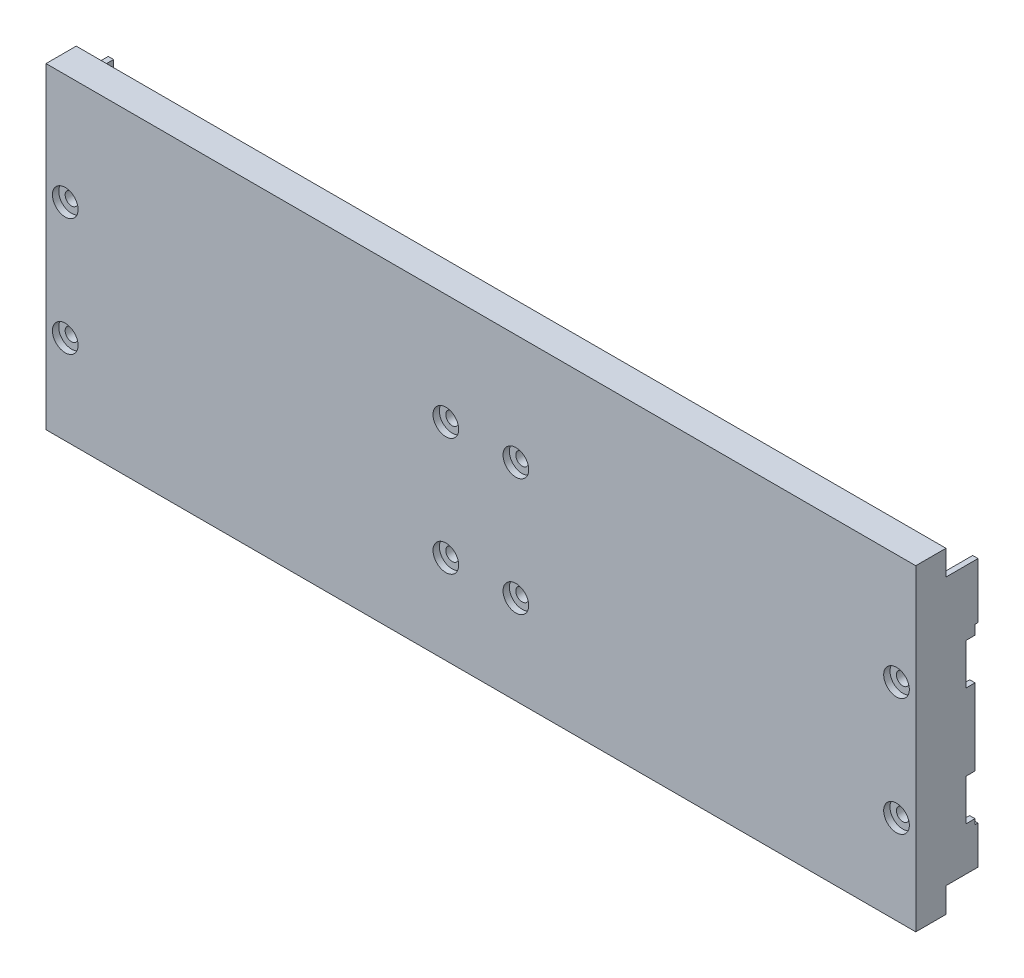
SolidWorks part; units mm, degrees
ref_plane "Front Plane" through (0, 0, 0) normal (0, 0, 1) x (1, 0, 0)
ref_plane "Top Plane" through (0, 0, 0) normal (0, 1, 0) x (1, 0, 0)
ref_plane "Right Plane" through (0, 0, 0) normal (1, 0, 0) x (0, 0, -1)
sketch "Sketch1" plane through (0, 0, 0) normal (0, 0, 1) x (1, 0, 0)
  line L0 (-30.5002, 35.0258) -> (66.0198, 35.0258) construction
  line L1 (67.5438, 35.0258) -> (-139.0852, 35.0258)
  line L2 (67.5438, 35.0258) -> (67.5438, -28.4742)
  line L3 (67.5438, -28.4742) -> (-139.0852, -28.4742)
  line L4 (-139.0852, 35.0258) -> (-139.0852, -28.4742)
  line L5 (66.0198, -28.4742) -> (-30.5002, -28.4742) construction
  line L6 (-137.5612, -28.4742) -> (-137.5612, 35.0258) construction
  line L7 (66.0198, 35.0258) -> (66.0198, -28.4742) construction
  dimension "D1" = 1.524
  dimension "D2" = 1.524
extrude "base" add sketch "Sketch1" along normal blind 5.08
sketch "Sketch2" plane through (0, 0, 0) normal (0, 0, -1) x (-1, 0, 0)
  line L0 (-67.5438, 35.0258) -> (139.0852, 35.0258) construction
  line L1 (137.5612, -26.9502) -> (-66.0198, -26.9502)
  line L2 (137.5612, -26.9502) -> (137.5612, 33.5018)
  line L3 (137.5612, 33.5018) -> (-66.0198, 33.5018)
  line L4 (-66.0198, -26.9502) -> (-66.0198, 33.5018)
  line L5 (-67.5438, -28.4742) -> (-67.5438, 35.0258) construction
  line L6 (139.0852, -28.4742) -> (-67.5438, -28.4742) construction
  line L7 (139.0852, 35.0258) -> (139.0852, -28.4742) construction
  dimension "D1" = 1.524
  dimension "D2" = 1.524
  dimension "D3" = 1.524
  dimension "D4" = 1.524
extrude "hollow" cut sketch "Sketch2" against normal blind 2
sketch "Sketch3" plane through (0, 0, 0) normal (0, 0, -1) x (-1, 0, 0)
  line L0 (-67.5438, 35.0258) -> (139.0852, 35.0258) construction
  line L1 (137.8152, 35.0258) -> (139.0852, 35.0258)
  line L2 (137.8152, 35.0258) -> (137.8152, -28.4742)
  line L3 (137.8152, -28.4742) -> (139.0852, -28.4742)
  line L4 (139.0852, 35.0258) -> (139.0852, -28.4742)
  line L5 (139.0852, -28.4742) -> (-67.5438, -28.4742) construction
  line L7 (139.0852, 35.0258) -> (139.0852, -28.4742) construction
  line L9 (-67.5438, 35.0258) -> (-66.2738, 35.0258)
  line L10 (-67.5438, 35.0258) -> (-67.5438, -28.4742)
  line L11 (-67.5438, -28.4742) -> (-66.2738, -28.4742)
  line L12 (-66.2738, 35.0258) -> (-66.2738, -28.4742)
  dimension "D1" = 1.27
  dimension "D2" = 1.27
extrude "end pieces" add sketch "Sketch3" along normal blind 9
sketch "Sketch7" plane through (67.5438, 0, 0) normal (1, 0, 0) x (0, 0, -1)
  line L0 (9, 35.0258) -> (9, -28.4742) construction
  line L1 (6.7986, 9.8068) -> (9, 9.8068)
  line L2 (6.7986, 9.8068) -> (6.7986, 19.6048)
  line L3 (6.7986, 19.6048) -> (9, 19.6048)
  line L4 (9, 9.8068) -> (9, 19.6048)
  line L5 (6.9986, 19.4048) -> (16.7986, 19.4048) construction
  line L6 (6.9986, 19.4048) -> (6.9986, 10.0068) construction
  line L7 (6.9986, 10.0068) -> (16.7986, 10.0068) construction
  line L8 (6.9986, -17.9332) -> (16.7986, -17.9332) construction
  line L9 (6.7986, -18.1332) -> (9, -18.1332)
  line L10 (6.7986, -18.1332) -> (6.7986, -8.3352)
  line L11 (6.7986, -8.3352) -> (9, -8.3352)
  line L12 (9, -18.1332) -> (9, -8.3352)
  dimension "D1" = 0.2
  dimension "D2" = 0.2
  dimension "D3" = 0.2
  dimension "D4" = 0.2
extrude "where top intrudes" cut sketch "Sketch7" against normal through all
sketch "cable stop wings" [suppressed] plane through (0, 0, 5.08) normal (0, 0, 1) x (1, 0, 0)
  line L0 (-139.0852, 35.0258) -> (-139.0852, -28.4742) construction
  line L1 (-139.0852, -28.4742) -> (67.5438, -28.4742)
  line L2 (-139.0852, -28.4742) -> (-139.0852, -46.2542)
  line L3 (-139.0852, -46.2542) -> (67.5438, -46.2542)
  line L4 (67.5438, -28.4742) -> (67.5438, -46.2542)
  line L5 (67.5438, -28.4742) -> (67.5438, 35.0258) construction
  line L6 (-139.0852, -28.4742) -> (67.5438, -28.4742) construction
  line L8 (-139.0852, 35.0258) -> (67.5438, 35.0258)
  line L9 (-139.0852, 35.0258) -> (-139.0852, 52.8058)
  line L10 (-139.0852, 52.8058) -> (67.5438, 52.8058)
  line L11 (67.5438, 35.0258) -> (67.5438, 52.8058)
  dimension "D1" = 17.78
extrude "cable stop wing boss" [suppressed] add sketch "cable stop wings" against normal blind 1.5 separate body
sketch "cable stop wings alt" plane through (0, 0, 5.08) normal (0, 0, 1) x (1, 0, 0)
  line L1 (-139.0852, -28.4742) -> (67.5438, -28.4742)
  line L2 (-139.0852, -28.4742) -> (-139.0852, -33.4742)
  line L3 (-139.0852, -33.4742) -> (67.5438, -33.4742)
  line L4 (67.5438, -28.4742) -> (67.5438, -33.4742)
  line L5 (67.5438, 35.0258) -> (-139.0852, 35.0258) construction
  line L6 (-139.0852, -28.4742) -> (67.5438, -28.4742) construction
  line L8 (-139.0852, 35.0258) -> (67.5438, 35.0258)
  line L9 (-139.0852, 35.0258) -> (-139.0852, 40.0258)
  line L10 (-139.0852, 40.0258) -> (67.5438, 40.0258)
  line L11 (67.5438, 35.0258) -> (67.5438, 40.0258)
  line L12 (67.5438, -28.4742) -> (67.5438, 35.0258) construction
  line L13 (-139.0852, 35.0258) -> (-139.0852, -28.4742) construction
  dimension "D1" = 5
extrude "cable stop wing boss alt" add sketch "cable stop wings alt" against normal blind 1.5
sketch "Sketch4" plane through (0, 0, 2) normal (0, 0, -1) x (-1, 0, 0)
  circle A0 centre (-62.9718, 14.7058) radius 2.794
  circle A1 centre (-62.9718, -13.2342) radius 2.794
  circle A2 centre (27.4522, -13.2342) radius 2.794
  circle A3 centre (44.0892, -13.2342) radius 2.794
  circle A4 centre (27.4522, 14.7058) radius 2.794
  circle A5 centre (44.0892, 14.7058) radius 2.794
  circle A6 centre (134.5132, 14.7058) radius 2.794
  circle A7 centre (134.5132, -13.2342) radius 2.794
  dimension "D1" = 5.588
extrude "screw bosses" add sketch "Sketch4" along normal up to surface (2 mm away) up to face at (-35.7707, 3.2758, 0)
sketch "Sketch5" plane through (0, 0, 0) normal (0, 0, -1) x (-1, 0, 0)
  circle A0 centre (-62.9718, 14.7058) radius 1.524
  circle A1 centre (-62.9718, -13.2342) radius 1.524
  circle A2 centre (27.4522, 14.7058) radius 1.524
  circle A3 centre (27.4522, -13.2342) radius 1.524
  circle A4 centre (44.0892, -13.2342) radius 1.524
  circle A5 centre (134.5132, 14.7058) radius 1.524
  circle A6 centre (134.5132, -13.2342) radius 1.524
  circle A7 centre (44.0892, 14.7058) radius 1.524
  dimension "D1" = 3.048
extrude "screw holes" cut sketch "Sketch5" against normal through all
sketch "wing extensions" [suppressed] plane through (0, 0, 5.08) normal (0, 0, -1) x (-1, 0, 0)
  line L0 (136.3082, -28.3942) -> (136.3082, -19.3942) construction
  line L1 (-73.6398, 52.8058) -> (-66.2908, 52.8058)
  line L2 (-73.6398, 52.8058) -> (-73.6398, 35.0258)
  line L3 (-73.6398, 35.0258) -> (-66.2908, 35.0258)
  line L4 (145.1812, 52.8058) -> (145.1812, 35.0258)
  line L6 (137.5612, -26.9502) -> (137.5612, 33.5018) construction
  line L7 (-66.2738, 35.0258) -> (137.8152, 35.0258) construction
  line L8 (-66.2908, -46.2542) -> (137.8322, -46.2542) construction
  line L10 (39.4452, -28.4742) -> (32.0962, -28.4742)
  line L11 (39.4452, -28.4742) -> (39.4452, -46.2542)
  line L12 (-73.6398, -46.2542) -> (-66.2908, -46.2542)
  line L13 (-73.6398, -46.2542) -> (-73.6398, -28.4742)
  line L14 (-73.6398, -28.4742) -> (-66.2908, -28.4742)
  line L15 (145.1812, -46.2542) -> (145.1812, -28.4742)
  line L16 (39.4452, -46.2542) -> (32.0962, -46.2542)
  line L17 (32.0962, -28.4742) -> (32.0962, -46.2542)
  line L18 (-66.0198, 33.5018) -> (-66.0198, -26.9502) construction
  line L19 (139.0852, -46.2542) -> (-67.5438, -46.2542) construction
  line L20 (137.8322, 35.0258) -> (137.8322, 52.8058)
  line L21 (-66.2908, 35.0258) -> (-66.2908, 52.8058)
  line L22 (-66.2908, -28.4742) -> (-66.2908, -46.2542)
  line L23 (137.8322, -28.4742) -> (137.8322, -46.2542)
  line L24 (137.8322, -46.2542) -> (145.1812, -46.2542)
  line L25 (137.8322, -28.4742) -> (145.1812, -28.4742)
  line L26 (137.8322, 52.8058) -> (145.1812, 52.8058)
  line L27 (137.8322, 35.0258) -> (145.1812, 35.0258)
  line L28 (39.4452, -28.4742) -> (32.0962, -46.2542) construction
  line L29 (39.4452, -46.2542) -> (32.0962, -28.4742) construction
  line L30 (139.0852, -28.4742) -> (-67.5438, -28.4742) construction
  line L31 (-67.5438, 35.0258) -> (139.0852, 35.0258) construction
  line L32 (32.0962, 52.8058) -> (39.4452, 52.8058)
  line L38 (32.0962, 52.8058) -> (32.0962, 35.0258)
  line L39 (32.0962, 35.0258) -> (39.4452, 35.0258)
  line L46 (39.4452, 52.8058) -> (39.4452, 35.0258)
  point P30 (35.7707, -37.3642)
  point P37 (35.7707, -46.2542)
  dimension "D1" = 7.62
  dimension "D2" = 7.62
  dimension "D3" = 1.524
extrude "wingtip risers" [suppressed] add sketch "wing extensions" along normal blind 7.874
ref_point "Point1" [suppressed]
ref_point "Point2" [suppressed]
ref_point "Point3" [suppressed]
ref_point "Point4" [suppressed]
ref_axis "Axis1" [suppressed] through (69.9653, 43.9158, -2.794) along (-1, 0, 0)
ref_axis "Axis2" [suppressed] through (69.9653, -37.3642, -2.794) along (-1, 0, 0)
sketch "Sketch10" [suppressed] plane through (0, 0, -2.794) normal (0, 0, -1) x (-1, 0, 0)
  line L0 (-66.2908, 52.8058) -> (-73.6398, 52.8058) construction
  line L1 (145.1812, 52.8058) -> (137.8322, 52.8058) construction
  line L3 (-73.6398, 35.0258) -> (-66.2908, 35.0258) construction
  line L4 (-73.6398, 52.8058) -> (-73.6398, 35.0258) construction
  line L5 (-66.2908, 35.0258) -> (-66.2908, 52.8058) construction
  line L6 (32.0962, 35.0258) -> (39.4452, 35.0258) construction
  circle A0 centre (-69.9653, 50.5198) radius 1.8288
  circle A1 centre (141.5067, 50.5198) radius 1.8288
  circle A2 centre (35.7707, 50.5198) radius 1.8288
  point P5 (-69.9653, 52.8058)
  point P10 (141.5067, 52.8058)
  point P21 (-69.9653, 35.0258)
  point P24 (35.7707, 35.0258)
  dimension "D1" = 3.6576
  dimension "D2" = 2.286
revolve "cable retention tunnel 1" [suppressed] cut sketch "Sketch10" angle 180 about axis through (69.9653, 43.9158, -2.794) along (-1, 0, 0) reverse direction yes
sketch "Sketch11" [suppressed] plane through (0, 0, -2.794) normal (0, 0, -1) x (-1, 0, 0)
  line L0 (-67.5438, -28.4742) -> (-73.6398, -28.4742) construction
  line L2 (137.8322, -46.2542) -> (145.1812, -46.2542) construction
  line L3 (-73.6398, -46.2542) -> (-66.2908, -46.2542) construction
  line L5 (32.0962, -46.2542) -> (39.4452, -46.2542) construction
  circle A0 centre (-69.9653, -30.7602) radius 1.8288
  circle A1 centre (35.7707, -30.7602) radius 1.8288
  circle A2 centre (141.5067, -30.7602) radius 1.8288
  circle A3 centre (-69.9653, 37.3118) radius 1.8288 construction
  point P18 (141.5067, -46.2542)
  point P22 (-69.9653, -46.2542)
  point P24 (35.7707, -46.2542)
  dimension "D1" = 2.286
revolve "cable retention tunnel 2" [suppressed] cut sketch "Sketch11" angle 180 about axis through (69.9653, -37.3642, -2.794) along (-1, 0, 0) reverse direction yes
fillet "Fillet1" [suppressed] radius 0.889
sketch "Sketch12" [suppressed] plane through (0, 0, 5.08) normal (0, 0, 1) x (1, 0, 0)
  line L0 (-145.1812, 52.8058) -> (73.6398, 52.8058) construction
  line L1 (-145.1812, 35.0258) -> (-145.1812, 52.8058) construction
  line L3 (-145.1812, -46.2542) -> (73.6398, -46.2542) construction
  line L4 (58.3998, 47.7258) -> (73.6398, 47.7258) construction
  line L5 (73.6398, 52.8058) -> (73.6398, 35.0258) construction
  line L6 (-129.9412, 47.7258) -> (-145.1812, 47.7258) construction
  line L7 (-145.1812, 35.0258) -> (-145.1812, 52.8058) construction
  circle A0 centre (-129.9412, 47.7258) radius 2.032
  circle A1 centre (-129.9412, 40.1058) radius 2.032
  circle A2 centre (-129.9412, -33.5542) radius 2.032
  circle A3 centre (-129.9412, -41.1742) radius 2.032
  circle A4 centre (58.3998, -41.1742) radius 2.032
  circle A5 centre (58.3998, -33.5542) radius 2.032
  circle A6 centre (58.3998, 40.1058) radius 2.032
  circle A7 centre (58.3998, 47.7258) radius 2.032
  dimension "D1" = 4.064
  dimension "D2" = 12.7
  dimension "D3" = 5.08
  dimension "D4" = 15.24
  dimension "D6" = 5.08
  dimension "D7" = 12.7
extrude "screw holes on wings" [suppressed] cut sketch "Sketch12" against normal through all
sketch "Sketch6" plane through (0, 0, 5.08) normal (0, 0, 1) x (1, 0, 0)
  circle A0 centre (62.9718, -13.2342) radius 3.048
  circle A1 centre (62.9718, 14.7058) radius 3.048
  circle A2 centre (-27.4522, -13.2342) radius 3.048
  circle A3 centre (-44.0892, -13.2342) radius 3.048
  circle A4 centre (-27.4522, 14.7058) radius 3.048
  circle A5 centre (-44.0892, 14.7058) radius 3.048
  circle A6 centre (-134.5132, 14.7058) radius 3.048
  circle A7 centre (-134.5132, -13.2342) radius 3.048
  dimension "D1" = 6.096
extrude "counter sink" cut sketch "Sketch6" against normal blind 1.5
sketch "Sketch13" [suppressed] plane through (-145.1812, 0, 0) normal (-1, 0, 0) x (0, 0, 1)
  line L0 (-2.794, -46.2542) -> (-2.794, -28.4742) construction
  line L1 (-2.794, 35.0258) -> (-2.794, 52.8058) construction
  circle A0 centre (-2.794, -37.3642) radius 4.191
  circle A1 centre (-2.794, 43.9158) radius 4.191
  dimension "D1" = 8.382
extrude "cable hollow" [suppressed] cut sketch "Sketch13" against normal through all
sketch "Sketch14" plane through (0, 0, 5.08) normal (0, 0, 1) x (1, 0, 0)
  line L5 (35.9798, 34.9458) -> (65.9798, 34.9458) construction
  line L6 (59.8698, 34.9458) -> (42.0898, 34.9458)
  line L7 (59.8698, 34.9458) -> (59.8698, 40.0258)
  line L8 (59.8698, 40.0258) -> (42.0898, 40.0258)
  line L9 (42.0898, 34.9458) -> (42.0898, 40.0258)
  line L10 (59.8698, 34.9458) -> (42.0898, 40.0258) construction
  line L11 (59.8698, 40.0258) -> (42.0898, 34.9458) construction
  line L12 (33.5728, 34.9458) -> (3.5728, 34.9458) construction
  line L13 (1.4638, 34.9458) -> (-28.5362, 34.9458) construction
  line L15 (-22.4262, 40.0258) -> (-4.6462, 40.0258)
  line L16 (-22.4262, 40.0258) -> (-22.4262, 34.9458)
  line L17 (-22.4262, 34.9458) -> (-4.6462, 34.9458)
  line L18 (-4.6462, 40.0258) -> (-4.6462, 34.9458)
  line L19 (-22.4262, 40.0258) -> (-4.6462, 34.9458) construction
  line L20 (-22.4262, 34.9458) -> (-4.6462, 40.0258) construction
  line L21 (9.6828, 34.9458) -> (27.4628, 34.9458)
  line L22 (9.6828, 34.9458) -> (9.6828, 40.0258)
  line L23 (9.6828, 40.0258) -> (27.4628, 40.0258)
  line L24 (27.4628, 34.9458) -> (27.4628, 40.0258)
  line L25 (9.6828, 34.9458) -> (27.4628, 40.0258) construction
  line L26 (9.6828, 40.0258) -> (27.4628, 34.9458) construction
  line L27 (67.5438, 40.0258) -> (-139.0852, 40.0258) construction
  point P0 (50.9798, 37.4858)
  point P7 (50.9798, 34.9458)
  point P18 (-13.5362, 37.4858)
  point P23 (18.5728, 37.4858)
  point P28 (18.5728, 34.9458)
  point P29 (-13.5362, 34.9458)
  dimension "D1" = 17.78
  dimension "D2" = 5.08
extrude "anchors-output" [suppressed] add sketch "Sketch14" against normal blind 7.62
sketch "Sketch15" plane through (0, 0, 5.08) normal (0, 0, -1) x (-1, 0, 0)
  line L0 (-65.5698, -28.3942) -> (-35.5698, -28.3942) construction
  line L1 (-59.4598, -28.3942) -> (-41.6798, -28.3942)
  line L2 (-59.4598, -28.3942) -> (-59.4598, -33.4742)
  line L3 (-59.4598, -33.4742) -> (-41.6798, -33.4742)
  line L4 (-41.6798, -28.3942) -> (-41.6798, -33.4742)
  line L5 (-59.4598, -28.3942) -> (-41.6798, -33.4742) construction
  line L6 (-59.4598, -33.4742) -> (-41.6798, -28.3942) construction
  line L7 (-27.0528, -28.3942) -> (-9.2728, -28.3942)
  line L8 (-27.0528, -28.3942) -> (-27.0528, -33.4742)
  line L9 (-27.0528, -33.4742) -> (-9.2728, -33.4742)
  line L10 (-9.2728, -28.3942) -> (-9.2728, -33.4742)
  line L11 (-27.0528, -28.3942) -> (-9.2728, -33.4742) construction
  line L12 (-27.0528, -33.4742) -> (-9.2728, -28.3942) construction
  line L13 (5.3572, -28.3942) -> (23.1372, -28.3942)
  line L14 (5.3572, -28.3942) -> (5.3572, -33.4742)
  line L15 (5.3572, -33.4742) -> (23.1372, -33.4742)
  line L16 (23.1372, -28.3942) -> (23.1372, -33.4742)
  line L17 (5.3572, -28.3942) -> (23.1372, -33.4742) construction
  line L18 (5.3572, -33.4742) -> (23.1372, -28.3942) construction
  line L19 (-33.1628, -28.3942) -> (-3.1628, -28.3942) construction
  line L20 (-0.7528, -28.3942) -> (29.2472, -28.3942) construction
  line L21 (139.0852, -33.4742) -> (-67.5438, -33.4742) construction
  point P0 (-50.5698, -30.9342)
  point P5 (-18.1628, -30.9342)
  point P10 (14.2472, -30.9342)
  point P19 (-50.5698, -28.3942)
  point P24 (-18.1628, -28.3942)
  point P29 (14.2472, -28.3942)
  dimension "D1" = 5.08
  dimension "D2" = 17.78
extrude "anchors-input" [suppressed] add sketch "Sketch15" along normal blind 7.62
ref_point "anchor out 1 center" [suppressed]
ref_point "anchor out 2 center" [suppressed]
ref_point "anchor out 3 center" [suppressed]
ref_axis "anchor out 1 axis" [suppressed] through (50.9798, 54.0758, -2.54) along (0, 1, 0)
ref_axis "anchor out 2 axis" [suppressed] through (18.5728, 54.0758, -2.54) along (0, 1, 0)
ref_axis "anchor out 3 axis" [suppressed] through (-13.5362, 54.0758, -2.54) along (0, 1, 0)
sketch "Sketch16" [suppressed] plane through (0, 0, -2.54) normal (0, 0, -1) x (-1, 0, 0)
  line L0 (-59.8698, 51.5358) -> (-59.8698, 56.6158) construction
  circle A0 centre (-57.3298, 54.0758) radius 1.778
  point P4 (-59.8698, 54.0758)
  dimension "D1" = 3.556
  dimension "D2" = 2.54
revolve "anchor 1 out cut" [suppressed] cut sketch "Sketch16" angle 180 about axis through (50.9798, 54.0758, -2.54) along (0, 1, 0) reverse direction yes
sketch "Sketch17" [suppressed] plane through (0, 0, -2.54) normal (0, 0, -1) x (-1, 0, 0)
  line L1 (-27.4628, 51.5358) -> (-27.4628, 56.6158) construction
  circle A0 centre (-24.9228, 54.0758) radius 1.778
  point P5 (-27.4628, 54.0758)
  dimension "D1" = 3.556
  dimension "D2" = 2.54
revolve "anchor 2 out cut" [suppressed] cut sketch "Sketch17" angle 180 about axis through (18.5728, 54.0758, -2.54) along (0, 1, 0) reverse direction yes
sketch "Sketch18" [suppressed] plane through (0, 0, -2.54) normal (0, 0, -1) x (-1, 0, 0)
  line L0 (4.6462, 51.5358) -> (4.6462, 56.6158) construction
  circle A0 centre (7.1862, 54.0758) radius 1.778
  point P5 (4.6462, 54.0758)
  dimension "D2" = 3.556
  dimension "D1" = 2.54
revolve "anchor 3 out cut" [suppressed] cut sketch "Sketch18" angle 180 about axis through (-13.5362, 54.0758, -2.54) along (0, 1, 0) reverse direction yes
sketch "Sketch20" [suppressed] plane through (0, 51.5358, 0) normal (0, -1, 0) x (1, 0, 0)
  circle A0 centre (50.9798, -2.54) radius 3.81
  circle A1 centre (18.5728, -2.54) radius 3.81
  circle A2 centre (-13.5362, -2.54) radius 3.81
  dimension "D1" = 7.62
extrude "cable hollow alt out" [suppressed] cut sketch "Sketch20" against normal through all
ref_point "anchor in 1 center" [suppressed]
ref_point "anchor in 2 center" [suppressed]
ref_point "anchor in 3 center" [suppressed]
ref_axis "anchor in 1 axis" [suppressed] through (50.5698, -46.2542, -2.54) along (0, -1, 0)
ref_axis "anchor in 2 axis" [suppressed] through (18.1628, -46.2542, -2.54) along (0, -1, 0)
ref_axis "anchor in 3 axis" [suppressed] through (-14.2472, -46.2542, -2.54) along (0, -1, 0)
sketch "Sketch19" [suppressed] plane through (0, 0, -2.54) normal (0, 0, -1) x (-1, 0, 0)
  line L0 (-59.4598, -43.7142) -> (-59.4598, -48.7942) construction
  circle A0 centre (-56.9198, -46.2542) radius 1.778
  point P4 (-59.4598, -46.2542)
  dimension "D2" = 3.556
  dimension "D1" = 2.54
revolve "anchor 1 in cut" [suppressed] cut sketch "Sketch19" angle 180 about axis through (50.5698, -46.2542, -2.54) along (0, -1, 0)
sketch "Sketch21" [suppressed] plane through (0, 0, -2.54) normal (0, 0, -1) x (-1, 0, 0)
  line L0 (-27.0528, -43.7142) -> (-27.0528, -48.7942) construction
  line L1 (-27.0528, -43.7142) -> (-27.0528, -48.7942) construction
  circle A0 centre (-24.5128, -46.2542) radius 1.778
  point P4 (-27.0528, -46.2542)
  dimension "D2" = 3.556
  dimension "D1" = 2.54
revolve "anchor 2 in cut" [suppressed] cut sketch "Sketch21" angle 180 about axis through (18.1628, -46.2542, -2.54) along (0, -1, 0)
sketch "Sketch22" [suppressed] plane through (0, 0, -2.54) normal (0, 0, -1) x (-1, 0, 0)
  line L0 (5.3572, -43.7142) -> (5.3572, -48.7942) construction
  circle A0 centre (7.8972, -46.2542) radius 1.778
  point P4 (5.3572, -46.2542)
  dimension "D2" = 3.556
  dimension "D1" = 2.54
revolve "anchor 3 in cut" [suppressed] cut sketch "Sketch22" angle 180 about axis through (-14.2472, -46.2542, -2.54) along (0, -1, 0)
sketch "Sketch23" [suppressed] plane through (0, -43.7142, 0) normal (0, 1, 0) x (1, 0, 0)
  circle A0 centre (-14.2472, 2.54) radius 3.81
  circle A1 centre (18.1628, 2.54) radius 3.81
  circle A2 centre (50.5698, 2.54) radius 3.81
  dimension "D1" = 7.62
extrude "cable hollow alt in" [suppressed] cut sketch "Sketch23" against normal through all
pattern_linear "LPattern1" [suppressed] count 2 spacing 106.9975 of bodies 129
sketch "Sketch24" [suppressed] plane through (0, 0, 5.08) normal (0, 0, 1) x (1, 0, 0)
  line L0 (67.5438, -28.4742) -> (59.4598, -48.7942)
  line L1 (59.4598, -48.7942) -> (67.5438, -48.7942)
  line L2 (67.5438, -48.7942) -> (67.5438, -28.4742)
  line L3 (59.8698, 56.6158) -> (67.5438, 35.0258)
  line L4 (67.5438, 35.0258) -> (67.5438, 56.6158)
  line L5 (67.5438, 56.6158) -> (59.8698, 56.6158)
  line L7 (-139.0852, 35.0258) -> (-129.4237, 56.6158)
  line L8 (-129.4237, 56.6158) -> (-139.0852, 56.6158)
  line L9 (-139.0852, 56.6158) -> (-139.0852, 35.0258)
  line L10 (-139.0852, -28.4742) -> (-130.1347, -48.7942)
  line L11 (-130.1347, -48.7942) -> (-139.0852, -48.7942)
  line L12 (-139.0852, -48.7942) -> (-139.0852, -28.4742)
extrude "remove corners" [suppressed] cut sketch "Sketch24" against normal through all both and the other way through all
sketch "Sketch25" plane through (0, 0, 5.08) normal (0, 0, 1) x (1, 0, 0)
  line L0 (-105.8162, 35.9458) -> (-135.1786, 35.9458) construction
  line L1 (-139.0852, 40.9458) -> (67.5438, 40.9458)
  line L2 (-139.0852, 40.9458) -> (-139.0852, 36.4458)
  line L3 (-139.0852, 36.4458) -> (67.5438, 36.4458)
  line L4 (67.5438, 40.9458) -> (67.5438, 36.4458)
  line L7 (67.5438, -34.3942) -> (-139.0852, -34.3942)
  line L8 (67.5438, -34.3942) -> (67.5438, -29.8942)
  line L9 (67.5438, -29.8942) -> (-139.0852, -29.8942)
  line L10 (-139.0852, -34.3942) -> (-139.0852, -29.8942)
  line L13 (-139.0852, 40.0258) -> (-139.0852, -33.4742) construction
  line L14 (67.5438, -33.4742) -> (67.5438, 40.0258) construction
  line L15 (-135.5901, -29.3942) -> (-106.2277, -29.3942) construction
  dimension "D1" = 0.5
  dimension "D2" = 5
  dimension "D3" = 0.5
  dimension "D4" = 5
extrude "box under connectors" add sketch "Sketch25" against normal offset from surface (7.1786 mm away) 3.81
sketch "Sketch26" plane through (-139.0852, 0, 0) normal (-1, 0, 0) x (0, 0, 1)
  line L0 (-2.0986, 40.9458) -> (5.08, 40.9458) construction
  line L1 (-2.0986, -34.3942) -> (5.08, -34.3942)
  line L2 (-2.0986, -34.3942) -> (-2.0986, 40.9458)
  line L3 (-2.0986, 40.9458) -> (5.08, 40.9458)
  line L4 (5.08, -34.3942) -> (5.08, 40.9458)
  line L5 (-2.0986, -34.3942) -> (5.08, -34.3942) construction
extrude "Fill ends" add sketch "Sketch26" against normal blind 1.5
extrude "Fill the other end" add sketch "Sketch26<2>" along normal blind 1.5 from surface starting at face at (67.5438, 2.2598, -3.2554)
sketch "Sketch26<2>" plane through (-139.0852, 0, 0) normal (-1, 0, 0) x (0, 0, 1) same geometry as "Sketch26"
sketch "Sketch27" plane through (-139.0852, 0, 0) normal (-1, 0, 0) x (0, 0, 1)
  line L0 (-10.2086, -28.4742) -> (-10.2086, -18.8862) construction
  line L1 (-9, -28.4742) -> (-9.7086, -28.4742)
  line L2 (-9, -28.4742) -> (-9, -19.3862)
  line L3 (-9, -19.3862) -> (-9.7086, -19.3862)
  line L4 (-9.7086, -28.4742) -> (-9.7086, -19.3862)
  line L5 (-9, -18.8862) -> (-10.2086, -18.8862) construction
  line L6 (-9, 21.3568) -> (-10.2086, 21.3568) construction
  line L7 (-9, 35.0258) -> (-9.7086, 35.0258)
  line L8 (-9, 35.0258) -> (-9, 21.8568)
  line L9 (-9, 21.8568) -> (-9.7086, 21.8568)
  line L10 (-9.7086, 35.0258) -> (-9.7086, 21.8568)
  line L11 (-10.2086, 21.3568) -> (-10.2086, 35.0258) construction
  dimension "D1" = 0.5
  dimension "D2" = 0.5
  dimension "D3" = 0.5
  dimension "D4" = 0.5
extrude "Boss-Extrude4" add sketch "Sketch27" against normal up to vertex (1.27 mm away) up to point (-137.8152, 35.0258, -9)
extrude "Boss-Extrude5" add sketch "Sketch27<2>" along normal up to vertex (-205.359 mm away) from surface up to point (66.2738, 35.0258, -9) starting at face at (67.5438, 2.0058, -4.9643)
sketch "Sketch27<2>" plane through (-139.0852, 0, 0) normal (-1, 0, 0) x (0, 0, 1) same geometry as "Sketch27"
